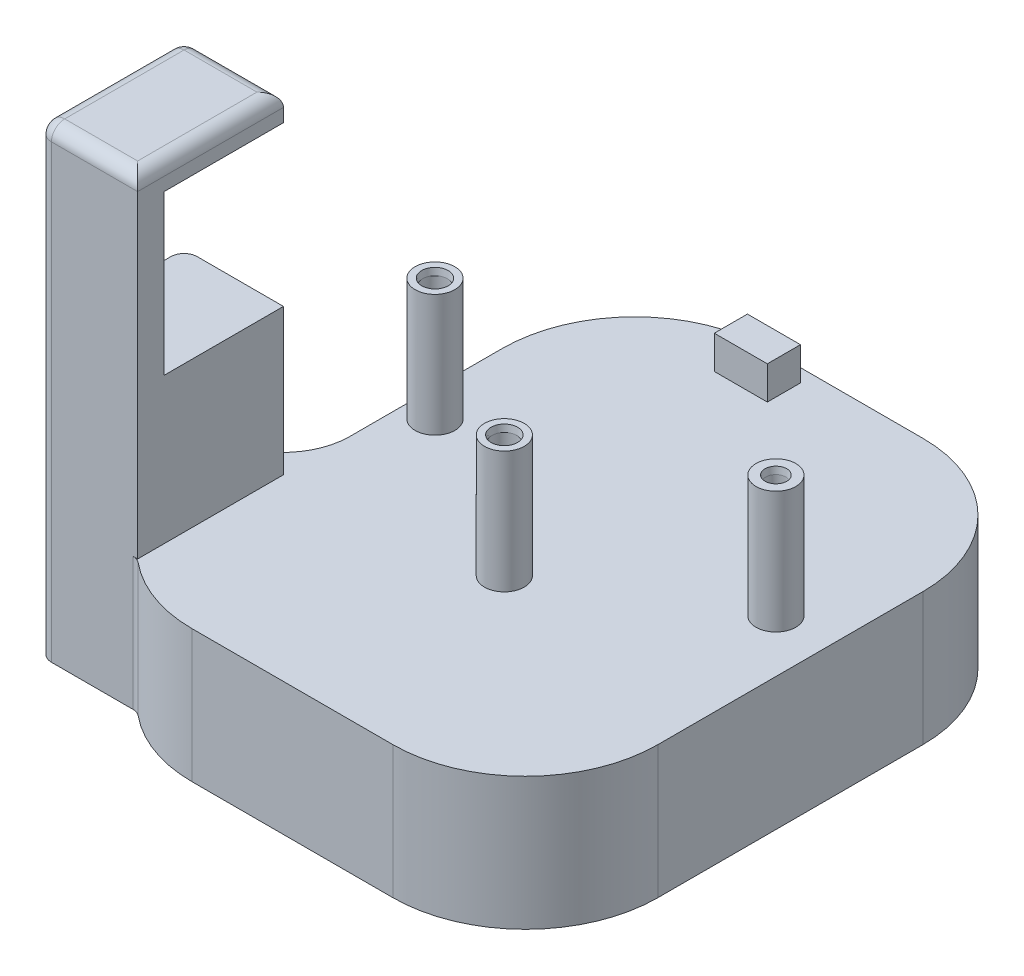
SolidWorks part; units mm, degrees
ref_plane "Front Plane" through (0, 0, 0) normal (0, 0, 1) x (1, 0, 0)
ref_plane "Top Plane" through (0, 0, 0) normal (0, 1, 0) x (1, 0, 0)
ref_plane "Right Plane" through (0, 0, 0) normal (1, 0, 0) x (0, 0, -1)
sketch "Sketch5" plane through (0, 0, 0) normal (0, 1, 0) x (1, 0, 0)
  line L1 (31.75, 40) -> (-31.75, 40)
  line L2 (31.75, 40) -> (31.75, -40)
  line L3 (31.75, -40) -> (-31.75, -40)
  line L4 (-31.75, 40) -> (-31.75, -40)
  line L5 (31.75, 40) -> (-31.75, -40) construction
  line L6 (31.75, -40) -> (-31.75, 40) construction
  point P0 (0, 0)
  dimension "D1" = 80
  dimension "D2" = 63.5
extrude "Boss-Extrude4" add sketch "Sketch5" along normal blind 20
sketch "Sketch6" plane through (0, 20, 0) normal (0, 1, 0) x (1, 0, 0)
  line L0 (31.75, 40) -> (-31.75, 40) construction
  line L1 (-4.75, 38) -> (-12.75, 38)
  line L2 (-4.75, 38) -> (-4.75, 33)
  line L3 (-4.75, 33) -> (-12.75, 33)
  line L4 (-12.75, 38) -> (-12.75, 33)
  line L5 (-4.75, 38) -> (-12.75, 33) construction
  line L6 (-4.75, 33) -> (-12.75, 38) construction
  line L9 (0, 0) -> (0, 40) construction
  line L10 (-31.75, 40) -> (-31.75, -40) construction
  point P0 (-8.75, 35.5)
  dimension "D1" = 8
  dimension "D2" = 5
  dimension "D3" = 2
  dimension "D4" = 19
extrude "Boss-Extrude5" add sketch "Sketch6" along normal blind 5 contours L3 L4 L1 L2
sketch "Sketch9" plane through (0, 0, 0) normal (0, 1, 0) x (1, 0, 0)
  line L0 (-31.75, 40) -> (-31.75, -40) construction
  line L5 (-31.75, -35) -> (-46.75, -35)
  line L6 (-31.75, -35) -> (-31.75, -13)
  line L7 (-31.75, -13) -> (-46.75, -13)
  line L8 (-46.75, -35) -> (-46.75, -13)
  line L9 (-31.75, -40) -> (31.75, -40) construction
  point P13 (-39.25, -13)
  dimension "D4" = 5
  dimension "D5" = 22
  dimension "D6" = 7.5
sketch "Sketch13" plane through (0, 20, 0) normal (0, 1, 0) x (1, 0, 0)
  line L0 (-31.75, 40) -> (-31.75, -40) construction
  line L2 (-31.75, -40) -> (31.75, -40) construction
  circle A0 centre (-27.6098, 5.72) radius 3
  circle A1 centre (23.8252, 5.72) radius 3
  circle A2 centre (-1.905, -9.52) radius 3
  dimension "D1" = 4.1402
  dimension "D3" = 6
  dimension "D4" = 51.435
  dimension "D6" = 6
  dimension "D7" = 6
  dimension "D2" = 45.72
  dimension "D5" = 45.72
  dimension "D8" = 25.7048
  dimension "D9" = 15.24
extrude "Boss-Extrude8" add sketch "Sketch13" along normal blind 18.4
extrude "Boss-Extrude10" add sketch "Sketch9" along normal blind 70 contours L8 L7 L6 L5
sketch "Sketch14" plane through (0, 0, 13) normal (0, 0, -1) x (-1, 0, 0)
  line L0 (31.75, 70) -> (31.75, 20) construction
  line L1 (31.75, 42) -> (46.75, 42)
  line L2 (31.75, 42) -> (31.75, 66)
  line L3 (31.75, 66) -> (46.75, 66)
  line L4 (46.75, 42) -> (46.75, 66)
  line L5 (46.75, 70) -> (46.75, 0) construction
  line L7 (31.75, 0) -> (46.75, 0) construction
  dimension "D1" = 42
  dimension "D2" = 24
extrude "Cut-Extrude1" cut sketch "Sketch14" against normal blind 18 contours L3 L4 L1 L2
fillet "Fillet1" radius 20 4 edges at (-31.75, 10, -40) (31.75, 10, -40) (-31.75, 10, 40) (31.75, 10, 40)
fillet "Fillet2" radius 10 1 edges at (-31.75, 10, 13)
fillet "Fillet3" radius 2 3 edges at (-31.75, 10, 35) (-46.75, 35, 35) (-46.75, 21, 13)
fillet "Fillet4" radius 2 1 edges at (-46.75, 68, 13)
fillet "Fillet6" radius 2 6 edges at (-31.75, 70, 24) (-38.25, 70, 35) (-46.1642, 70, 34.4142) (-46.75, 70, 24) (-46.1642, 70, 13.5858) (-38.25, 70, 13)
sketch "Sketch15" plane through (0, 38.4, 0) normal (0, 1, 0) x (1, 0, 0)
  circle A0 centre (23.8252, 5.72) radius 1.6383
  circle A1 centre (23.8252, 5.72) radius 3 construction
  circle A2 centre (-1.905, -9.52) radius 2
  circle A5 centre (-27.6098, 5.72) radius 2
  dimension "D1" = 3.2766
  dimension "D3" = 4
  dimension "D4" = 4
  dimension "D2" = 0
extrude "Cut-Extrude2" cut sketch "Sketch15" against normal blind 1 draft 8
sketch "Sketch16" plane through (0, 37.4, 0) normal (0, 1, 0) x (1, 0, 0)
  circle A0 centre (23.8252, 5.72) radius 1.4986
  circle A1 centre (23.8252, 5.72) radius 3 construction
  circle A2 centre (-1.905, -9.52) radius 2
  circle A3 centre (-27.6098, 5.72) radius 2
  dimension "D1" = 2.9972
  dimension "D3" = 4
  dimension "D4" = 4
  dimension "D2" = 0
extrude "Cut-Extrude3" cut sketch "Sketch16" against normal blind 7
